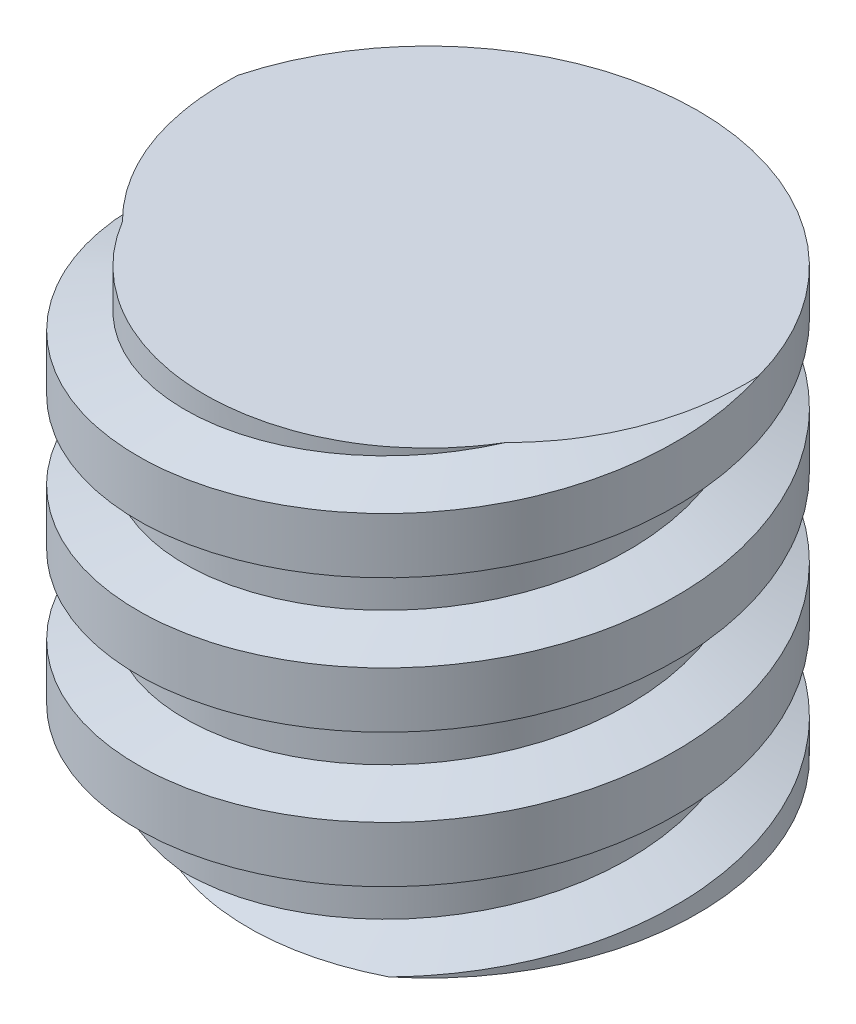
SolidWorks part; units mm, degrees
ref_plane "Спереди" through (0, 0, 0) normal (0, 0, 1) x (1, 0, 0)
ref_plane "Сверху" through (0, 0, 0) normal (0, 1, 0) x (1, 0, 0)
ref_plane "Справа" through (0, 0, 0) normal (1, 0, 0) x (0, 0, -1)
sketch "Эскиз3" plane through (0, 0, 0) normal (0, 0, 1) x (1, 0, 0)
  line L0 (0, 0) -> (0, 16.0133) construction
  line L1 (0, 0) -> (9.5, 0)
  line L2 (9.5, 0) -> (9.5, 15)
  line L3 (9.5, 15) -> (0, 15)
  line L4 (0, 15) -> (0, 0)
  line L5 (0, 16.0133) -> (15.8419, 16.0133) construction
  line L6 (0, 0) -> (0, 40.7619) construction
  dimension "D1" = 9.5
  dimension "D2" = 15
revolve "Повернуть1" add sketch "Эскиз3" angle 360 about L0
sketch "Эскиз6" plane through (0, 15, 0) normal (0, 1, 0) x (1, 0, 0)
  circle A1 centre (0, 0) radius 9.5
  circle A2 centre (0, 0) radius 9.5
  dimension "D1" = 0
curve "Спираль1" pitch 4.712 height 36.518 turns 7.75
sketch "Эскиз7" plane through (0, 0, 0) normal (1, 0, 0) x (0, 0, -1)
  line L0 (-9.5, 12.8871) -> (-9.5, -1.6217) construction
  line L1 (-9.5, 15) -> (-9.5, 0) construction
  line L2 (-9.5, 16.375) -> (-9.5, 13.625) construction
  line L4 (-7.85, 14.2256) -> (-7.85, 15.7744)
  line L5 (-7.85, 15.7744) -> (-11.15, 16.9756)
  line L6 (-11.15, 16.9756) -> (-11.15, 13.0244)
  line L7 (-11.15, 13.0244) -> (-7.85, 14.2256)
  line L9 (-11.15, 15) -> (-1.3827, 15) construction
  point P13 (-9.5, 15)
  dimension "D1" = 3.3
  dimension "D2" = 20
  dimension "D3" = 2.75
sweep "Вырез-По траектории1" cut profiles "Эскиз7" path "Спираль1" align with end faces yes
